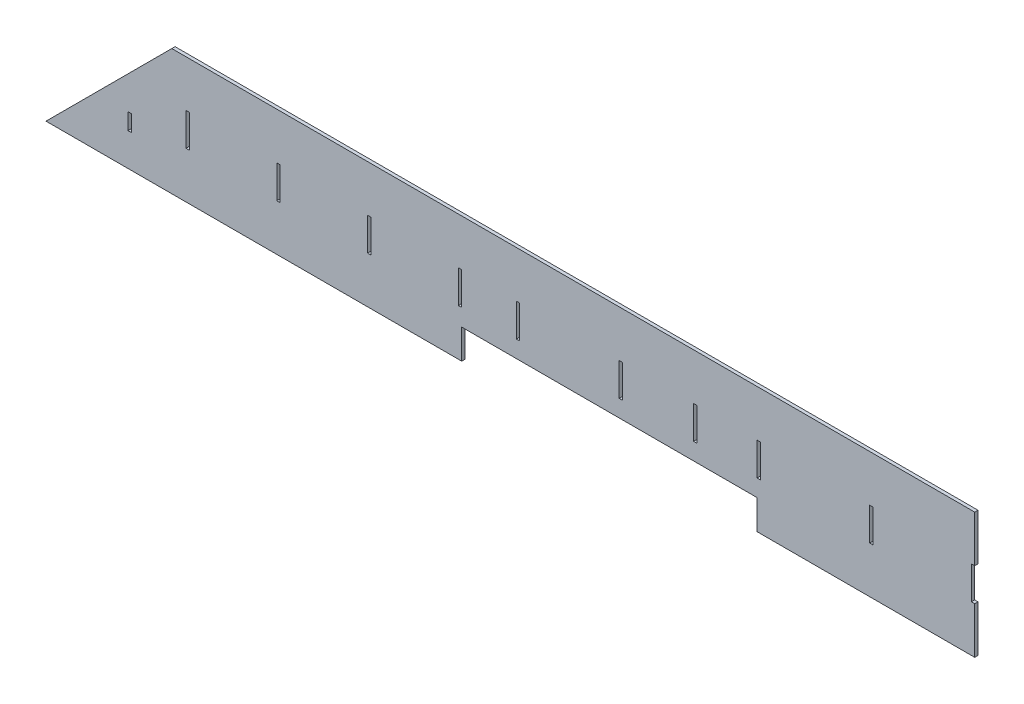
SolidWorks part; units mm, degrees
ref_plane "Front Plane" through (0, 0, 0) normal (0, 0, 1) x (1, 0, 0)
ref_plane "Top Plane" through (0, 0, 0) normal (0, 1, 0) x (1, 0, 0)
ref_plane "Right Plane" through (0, 0, 0) normal (1, 0, 0) x (0, 0, -1)
sketch "Sketch1" plane through (0, 0, 0) normal (0, 0, 1) x (1, 0, 0)
  line L0 (0, 0) -> (115, 115)
  line L1 (115, 115) -> (849, 115)
  line L3 (849, 0) -> (0, 0)
  line L4 (1244.614, 57.5) -> (-683.0281, 57.5) construction
  line L5 (128, 72.5) -> (131, 72.5)
  line L6 (128, 72.5) -> (128, 42.5)
  line L7 (128, 42.5) -> (131, 42.5)
  line L8 (131, 72.5) -> (131, 42.5)
  line L9 (75, 45) -> (78, 45)
  line L10 (75, 45) -> (75, 30)
  line L11 (75, 30) -> (78, 30)
  line L12 (78, 45) -> (78, 30)
  line L14 (211, 72.5) -> (214, 72.5)
  line L15 (211, 72.5) -> (211, 42.5)
  line L16 (211, 42.5) -> (214, 42.5)
  line L17 (214, 72.5) -> (214, 42.5)
  line L18 (294, 72.5) -> (297, 72.5)
  line L19 (294, 72.5) -> (294, 42.5)
  line L20 (294, 42.5) -> (297, 42.5)
  line L21 (297, 72.5) -> (297, 42.5)
  line L22 (377, 72.5) -> (380, 72.5)
  line L23 (377, 72.5) -> (377, 42.5)
  line L24 (377, 42.5) -> (380, 42.5)
  line L25 (380, 72.5) -> (380, 42.5)
  line L26 (430, 72.5) -> (433, 72.5)
  line L27 (430, 72.5) -> (430, 42.5)
  line L28 (430, 42.5) -> (433, 42.5)
  line L29 (433, 72.5) -> (433, 42.5)
  line L30 (524, 72.5) -> (527, 72.5)
  line L31 (524, 72.5) -> (524, 42.5)
  line L32 (524, 42.5) -> (527, 42.5)
  line L33 (527, 72.5) -> (527, 42.5)
  line L34 (592, 72.5) -> (595, 72.5)
  line L35 (592, 72.5) -> (592, 42.5)
  line L36 (592, 42.5) -> (595, 42.5)
  line L37 (595, 72.5) -> (595, 42.5)
  line L38 (650, 72.5) -> (653, 72.5)
  line L39 (650, 72.5) -> (650, 42.5)
  line L40 (650, 42.5) -> (653, 42.5)
  line L41 (653, 72.5) -> (653, 42.5)
  line L42 (753, 72.5) -> (756, 72.5)
  line L43 (753, 72.5) -> (753, 42.5)
  line L44 (753, 42.5) -> (756, 42.5)
  line L45 (756, 72.5) -> (756, 42.5)
  line L46 (846, 72.5) -> (849, 72.5)
  line L47 (846, 72.5) -> (846, 42.5)
  line L48 (846, 42.5) -> (849, 42.5)
  line L53 (849, 72.5) -> (849, 115)
  line L54 (849, 42.5) -> (849, 0)
  line L55 (75, 75) -> (75, 0) construction
  point P43 (846, 57.5)
  point P48 (75, 37.5)
  dimension "D1" = 115
  dimension "D2" = 30
  dimension "D3" = 3
  dimension "D4" = 15
  dimension "D5" = 3
  dimension "D6" = 75
  dimension "D7" = 50
  dimension "D8" = 30
  dimension "D9" = 3
  dimension "D10" = 30
  dimension "D11" = 3
  dimension "D12" = 80
  dimension "D13" = 80
  dimension "D14" = 80
  dimension "D15" = 3
  dimension "D16" = 30
  dimension "D17" = 50
  dimension "D18" = 3
  dimension "D19" = 30
  dimension "D20" = 91
  dimension "D21" = 3
  dimension "D22" = 30
  dimension "D23" = 65
  dimension "D24" = 30
  dimension "D25" = 3
  dimension "D26" = 55
  dimension "D27" = 3
  dimension "D28" = 30
  dimension "D29" = 3
  dimension "D30" = 30
  dimension "D31" = 100
  dimension "D32" = 90
  dimension "D33" = 3
  dimension "D34" = 30
  dimension "D35" = 45
extrude "Boss-Extrude1" add sketch "Sketch1" along normal blind 3
sketch "Sketch2" plane through (0, 0, 3) normal (0, 0, 1) x (1, 0, 0)
  line L0 (0, 0) -> (849, 0) construction
  line L1 (380, 0) -> (650, 0)
  line L2 (380, 0) -> (380, 27)
  line L3 (380, 27) -> (650, 27)
  line L4 (650, 0) -> (650, 27)
  line L6 (380, 42.5) -> (380, 72.5) construction
  line L7 (650, 72.5) -> (650, 42.5) construction
  dimension "D1" = 27
extrude "Cut-Extrude1" cut sketch "Sketch2" against normal blind 10
